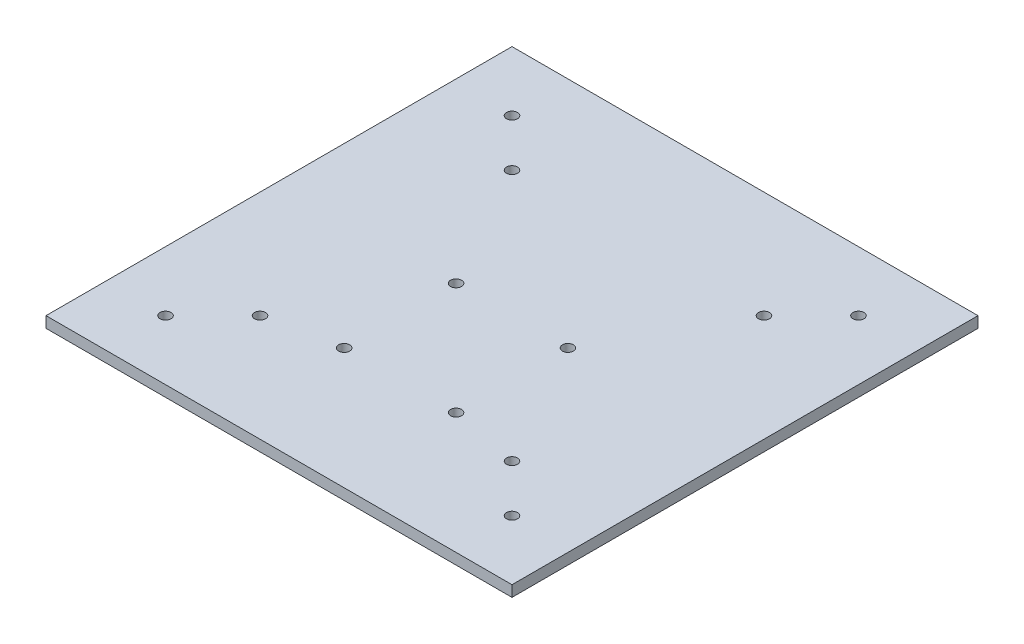
SolidWorks part; units mm, degrees
ref_plane "Front Plane" through (0, 0, 0) normal (0, 0, 1) x (1, 0, 0)
ref_plane "Top Plane" through (0, 0, 0) normal (0, 1, 0) x (1, 0, 0)
ref_plane "Right Plane" through (0, 0, 0) normal (1, 0, 0) x (0, 0, -1)
sketch "Sketch2" plane through (0, 0, 0) normal (0, 1, 0) x (1, 0, 0)
  line L1 (63.5, 63.5) -> (-63.5, 63.5)
  line L2 (63.5, 63.5) -> (63.5, -63.5)
  line L3 (63.5, -63.5) -> (-63.5, -63.5)
  line L4 (-63.5, 63.5) -> (-63.5, -63.5)
  line L5 (63.5, 63.5) -> (-63.5, -63.5) construction
  line L6 (63.5, -63.5) -> (-63.5, 63.5) construction
  point P0 (0, 0)
  dimension "D1" = 127
  dimension "D2" = 127
extrude "Boss-Extrude1" add sketch "Sketch2" along normal blind 3
sketch "Sketch3" plane through (0, 3, 0) normal (0, 1, 0) x (1, 0, 0)
  line L0 (-63.5, 63.5) -> (63.5, -63.5) construction
  line L1 (0, 63.5) -> (0, -63.5) construction
  line L2 (63.5, 63.5) -> (-63.5, 63.5) construction
  line L3 (-63.5, -63.5) -> (63.5, -63.5) construction
  circle A0 centre (-47.2147, 47.2147) radius 1.5
  circle A1 centre (-34.3371, 34.3371) radius 1.5
  circle A2 centre (47.2147, 47.2147) radius 1.5
  circle A3 centre (34.3371, 34.3371) radius 1.5
  circle A4 centre (47.2147, -47.2147) radius 1.5
  circle A5 centre (34.3371, -34.3371) radius 1.5
  circle A6 centre (-47.2147, -47.2147) radius 1.5
  circle A7 centre (-34.3371, -34.3371) radius 1.5
  point P28 (0, 0)
  dimension "D1" = 4
extrude "Cut-Extrude1" cut sketch "Sketch3" against normal through all both and the other way through all
sketch "Sketch4" plane through (0, 3, 0) normal (0, 1, 0) x (1, 0, 0)
  line L0 (0, 129.7192) -> (0, -138.5455) construction
  line L5 (15.25, -30.5) -> (-15.25, 0) construction
  line L6 (15.25, 0) -> (-15.25, -30.5) construction
  line L7 (0, 0) -> (-200.7917, 0) construction
  circle A0 centre (-15.25, 0) radius 1.5
  circle A1 centre (15.25, 0) radius 1.5
  circle A2 centre (-15.25, -30.5) radius 1.5
  circle A3 centre (15.25, -30.5) radius 1.5
  point P0 (0, -15.25)
  point P13 (0, 0)
  dimension "D1" = 30.5
  dimension "D2" = 30.5
extrude "Cut-Extrude2" cut sketch "Sketch4" against normal blind 10
